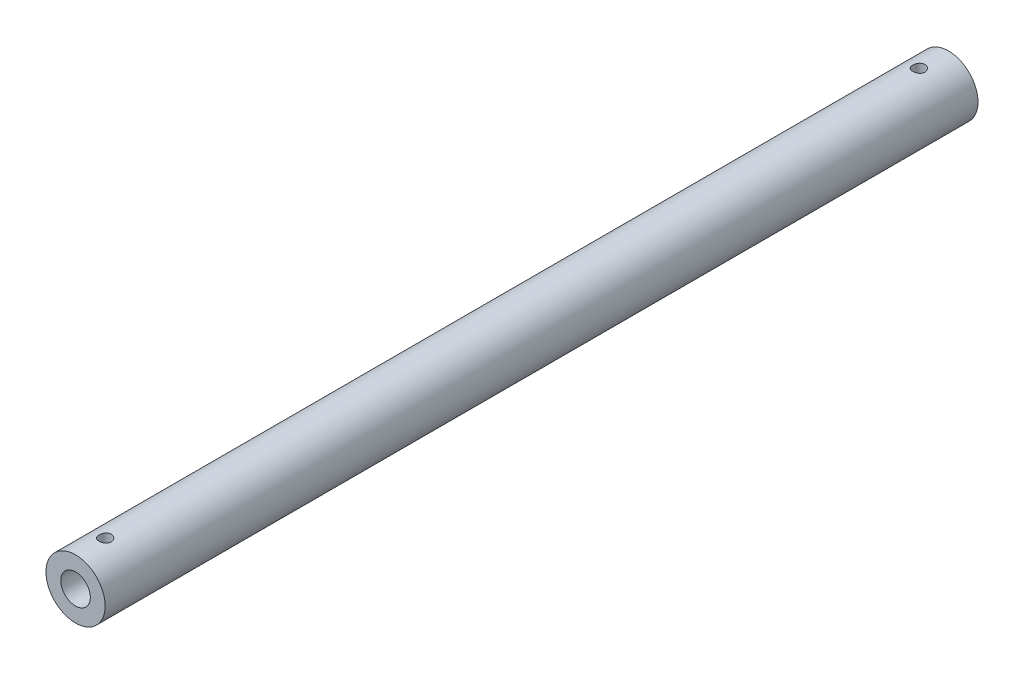
SolidWorks part; units mm, degrees
ref_plane "Front Plane" through (0, 0, 0) normal (0, 0, 1) x (1, 0, 0)
ref_plane "Top Plane" through (0, 0, 0) normal (0, 1, 0) x (1, 0, 0)
ref_plane "Right Plane" through (0, 0, 0) normal (1, 0, 0) x (0, 0, -1)
sketch "Sketch1" plane through (0, 0, 0) normal (0, 0, 1) x (1, 0, 0)
  circle A0 centre (0, 0) radius 15
  circle A1 centre (0, 0) radius 7.5
  dimension "D1" = 30
  dimension "D2" = 7.5
extrude "Boss-Extrude1" add sketch "Sketch1" along normal blind 221.25 and the other way blind 221.25
sketch "Sketch3" plane through (0, 0, 0) normal (0, 1, 0) x (1, 0, 0)
  line L0 (15, 221.25) -> (-15, 221.25) construction
  circle A0 centre (0, 206.25) radius 3.1
  dimension "D2" = 6.2
  dimension "D1" = 15
extrude "Cut-Extrude1" cut sketch "Sketch3" along normal through all
mirror "Mirror1" about plane through (0, 0, 0) normal (0, 0, 1) of "Cut-Extrude1"
